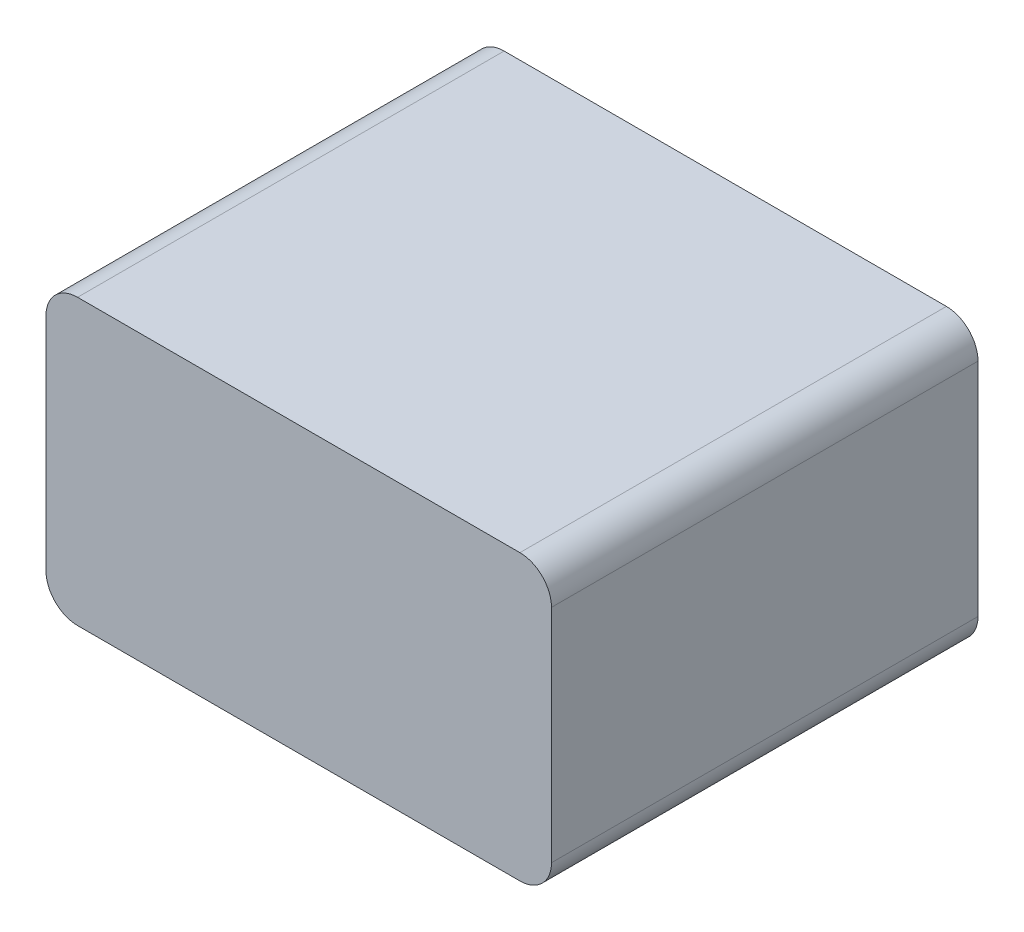
SolidWorks part; units mm, degrees
ref_plane "Front Plane" through (0, 0, 0) normal (0, 0, 1) x (1, 0, 0)
ref_plane "Top Plane" through (0, 0, 0) normal (0, 1, 0) x (1, 0, 0)
ref_plane "Right Plane" through (0, 0, 0) normal (1, 0, 0) x (0, 0, -1)
sketch "Sketch2" plane through (0, 0, 0) normal (0, 0, 1) x (1, 0, 0)
  line L0 (32.5, -20) -> (-32.5, -20) construction
  line L1 (37.5, 15) -> (37.5, -15) construction
  line L2 (-32.5, 20) -> (32.5, 20) construction
  line L3 (-37.5, -15) -> (-37.5, 15) construction
  line L4 (32.5, -20) -> (-32.5, -20)
  line L5 (37.5, 15) -> (37.5, -15)
  line L6 (-32.5, 20) -> (32.5, 20)
  line L7 (-37.5, -15) -> (-37.5, 15)
  line L9 (-35, -22.5) -> (35, -22.5)
  line L10 (-40, -17.5) -> (-40, 17.5)
  line L11 (-35, 22.5) -> (35, 22.5)
  line L12 (40, -17.5) -> (40, 17.5)
  line L13 (-40, -22.5) -> (40, 22.5) construction
  line L14 (-40, 22.5) -> (40, -22.5) construction
  arc A0 (-37.5, -15) -> (-32.5, -20) centre (-32.5, -15) ccw construction
  arc A1 (32.5, -20) -> (37.5, -15) centre (32.5, -15) ccw construction
  arc A2 (37.5, 15) -> (32.5, 20) centre (32.5, 15) ccw construction
  arc A3 (-32.5, 20) -> (-37.5, 15) centre (-32.5, 15) ccw construction
  circle A4 centre (-32.5, -15) radius 1.5 construction
  circle A5 centre (32.5, -15) radius 1.5 construction
  circle A6 centre (32.5, 15) radius 1.5 construction
  circle A7 centre (-32.5, 15) radius 1.5 construction
  arc A8 (-37.5, -15) -> (-32.5, -20) centre (-32.5, -15) ccw
  arc A9 (32.5, -20) -> (37.5, -15) centre (32.5, -15) ccw
  arc A10 (37.5, 15) -> (32.5, 20) centre (32.5, 15) ccw
  arc A11 (-32.5, 20) -> (-37.5, 15) centre (-32.5, 15) ccw
  circle A12 centre (-32.5, -15) radius 1.5
  circle A13 centre (32.5, -15) radius 1.5
  circle A14 centre (32.5, 15) radius 1.5
  circle A15 centre (-32.5, 15) radius 1.5
  arc A16 (35, 22.5) -> (40, 17.5) centre (35, 17.5) cw
  arc A17 (35, -22.5) -> (40, -17.5) centre (35, -17.5) ccw
  arc A18 (-35, -22.5) -> (-40, -17.5) centre (-35, -17.5) cw
  arc A19 (-40, 17.5) -> (-35, 22.5) centre (-35, 17.5) cw
  point P14 (0, 0)
  arc M3 (-32.5, 20) -> (-37.5, 15) centre (-32.5, 15) ccw
  line M4 (-37.5, 15) -> (-37.5, -15)
  arc M5 (-37.5, -15) -> (-32.5, -20) centre (-32.5, -15) ccw
  line M6 (-32.5, -20) -> (32.5, -20)
  arc M7 (32.5, -20) -> (37.5, -15) centre (32.5, -15) ccw
  line M8 (37.5, -15) -> (37.5, 15)
  arc M9 (37.5, 15) -> (32.5, 20) centre (32.5, 15) ccw
  line M10 (32.5, 20) -> (-32.5, 20)
  dimension "D3" = 5
  dimension "D1" = 2.5
  dimension "D2" = 2.5
extrude "Boss-Extrude1" add sketch "Sketch2" along normal blind 65 contours A19 L10 A18 L9 A17 L12 A16 L11 M3 M10 M9 M8 M7 M6 M5 M4 region at (-37.8865, -20.3865, 0)
sketch "Sketch3" plane through (0, 0, 65) normal (0, 0, 1) x (1, 0, 0)
  line L4 (-40, 17.5) -> (-40, -17.5)
  line L5 (-35, -22.5) -> (35, -22.5)
  line L6 (40, -17.5) -> (40, 17.5)
  line L7 (35, 22.5) -> (-35, 22.5)
  line L8 (-40, 17.5) -> (-40, -17.5)
  line L9 (-35, -22.5) -> (35, -22.5)
  line L10 (40, -17.5) -> (40, 17.5)
  line L11 (35, 22.5) -> (-35, 22.5)
  arc A4 (-35, 22.5) -> (-40, 17.5) centre (-35, 17.5) ccw
  arc A5 (-40, -17.5) -> (-35, -22.5) centre (-35, -17.5) ccw
  arc A6 (35, -22.5) -> (40, -17.5) centre (35, -17.5) ccw
  arc A7 (40, 17.5) -> (35, 22.5) centre (35, 17.5) ccw
  arc A8 (-35, 22.5) -> (-40, 17.5) centre (-35, 17.5) ccw
  arc A9 (-40, -17.5) -> (-35, -22.5) centre (-35, -17.5) ccw
  arc A10 (35, -22.5) -> (40, -17.5) centre (35, -17.5) ccw
  arc A11 (40, 17.5) -> (35, 22.5) centre (35, 17.5) ccw
  dimension "D1" = 0
extrude "Boss-Extrude2" add sketch "Sketch3" along normal blind 2.5 contours A8 L8 A9 L9 A10 L10 A11 L11
